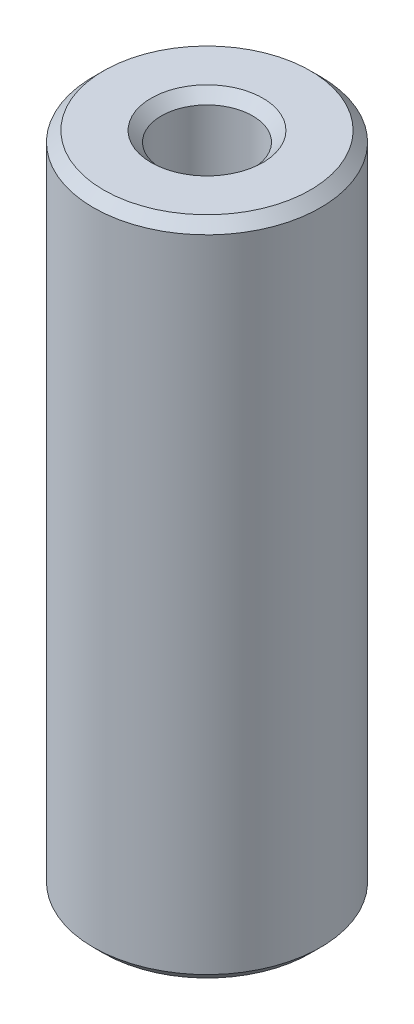
SolidWorks part; units mm, degrees
ref_plane "Front Plane" through (0, 0, 0) normal (0, 0, 1) x (1, 0, 0)
ref_plane "Top Plane" through (0, 0, 0) normal (0, 1, 0) x (1, 0, 0)
ref_plane "Right Plane" through (0, 0, 0) normal (1, 0, 0) x (0, 0, -1)
sketch "Sketch1" plane through (0, 0, 0) normal (0, 1, 0) x (1, 0, 0)
  circle A0 centre (0, 0) radius 12.5
  dimension "SLEEVE_OD" = 25
extrude "Boss-Extrude1" add sketch "Sketch1" along normal blind 72.7712
sketch "Sketch2" plane through (0, 0, 0) normal (0, 1, 0) x (1, 0, 0)
  circle A0 centre (0, 0) radius 5.0238
  dimension "BORE_D" = 10.0475
extrude "Cut-Extrude1" cut sketch "Sketch2" along normal through all
chamfer "Chamfer1" distance 1.1234 angle 45 4 edges at (0, 72.7712, 5.0238) (0, 0, 5.0238) (0, 0, 12.5) (0, 72.7712, 12.5)
